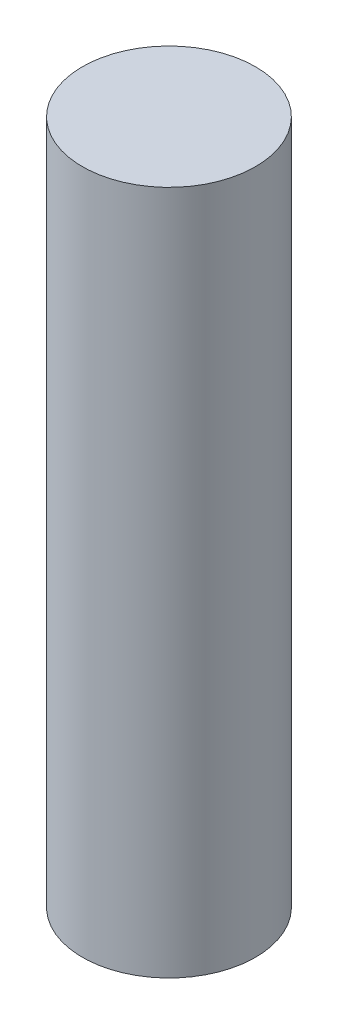
SolidWorks part; units mm, degrees
ref_plane "Plano frontal" through (0, 0, 0) normal (0, 0, 1) x (1, 0, 0)
ref_plane "Plano superior" through (0, 0, 0) normal (0, 1, 0) x (1, 0, 0)
ref_plane "Plano direito" through (0, 0, 0) normal (1, 0, 0) x (0, 0, -1)
sketch "Sketch1" plane through (0, 0, 0) normal (0, 0, 1) x (1, 0, 0)
  line L0 (0, 0) -> (11, 0)
  line L1 (11, 0) -> (11, 87)
  line L2 (11, 87) -> (0, 87)
  line L3 (0, 87) -> (0, 0)
  dimension "D1" = 11
  dimension "D2" = 87
revolve "Revolve4" add sketch "Sketch1" angle 360 about L1
